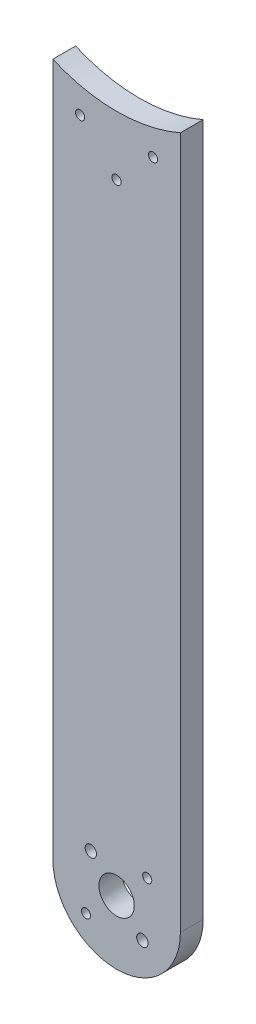
SolidWorks part; units mm, degrees
ref_plane "Front Plane" through (0, 0, 0) normal (0, 0, 1) x (1, 0, 0)
ref_plane "Top Plane" through (0, 0, 0) normal (0, 1, 0) x (1, 0, 0)
ref_plane "Right Plane" through (0, 0, 0) normal (1, 0, 0) x (0, 0, -1)
sketch "Sketch1" plane through (0, 0, 0) normal (0, 0, 1) x (1, 0, 0)
  line L0 (-14, 0) -> (-14, 151.9952)
  line L1 (0, 149.0732) -> (0, -14) construction
  line L2 (14, 0) -> (14, 151.9952)
  line L3 (-14, 0) -> (14, 0) construction
  line L4 (-5.6569, 5.6569) -> (5.6569, -5.6569) construction
  line L5 (0, 0) -> (-10.0045, -10.0045) construction
  line L6 (-10.0045, -10.0045) -> (8.2197, 8.2197) construction
  arc A0 (-14, 0) -> (14, 0) centre (0, 0) ccw
  arc A1 (-14, 151.9952) -> (14, 151.9952) centre (0, 184.0732) ccw
  circle A2 centre (-8, 144.3712) radius 1
  circle A3 centre (5.6569, -5.6569) radius 1.25
  circle A4 centre (-6.7175, -6.7175) radius 1
  circle A5 centre (6.7175, 6.7175) radius 1
  circle A6 centre (-5.6569, 5.6569) radius 1.25
  circle A7 centre (8, 144.3712) radius 1
  circle A8 centre (0, 136.0732) radius 1
  circle A9 centre (0, 136.0732) radius 1 construction
  circle A10 centre (-8, 144.3712) radius 1 construction
  circle A11 centre (8, 144.3712) radius 1 construction
  circle A13 centre (0, 184.0732) radius 35 construction
  circle A14 centre (-5.6569, 5.6569) radius 1.25 construction
  circle A15 centre (-6.7175, -6.7175) radius 1.25 construction
  circle A19 centre (5.6569, -5.6569) radius 1.25 construction
  dimension "D1" = 2.5
  dimension "D3" = 14
  dimension "D5" = 2
  dimension "D2" = 2
  dimension "D8" = 35
  dimension "D11" = 2
extrude "Boss-Extrude1" add sketch "Sketch1" along normal blind 5
sketch "Sketch2" plane through (0, 0, 5) normal (0, 0, 1) x (1, 0, 0)
  circle A0 centre (0, 0) radius 3.875
extrude "Cut-Extrude1" cut sketch "Sketch2" against normal up to next
